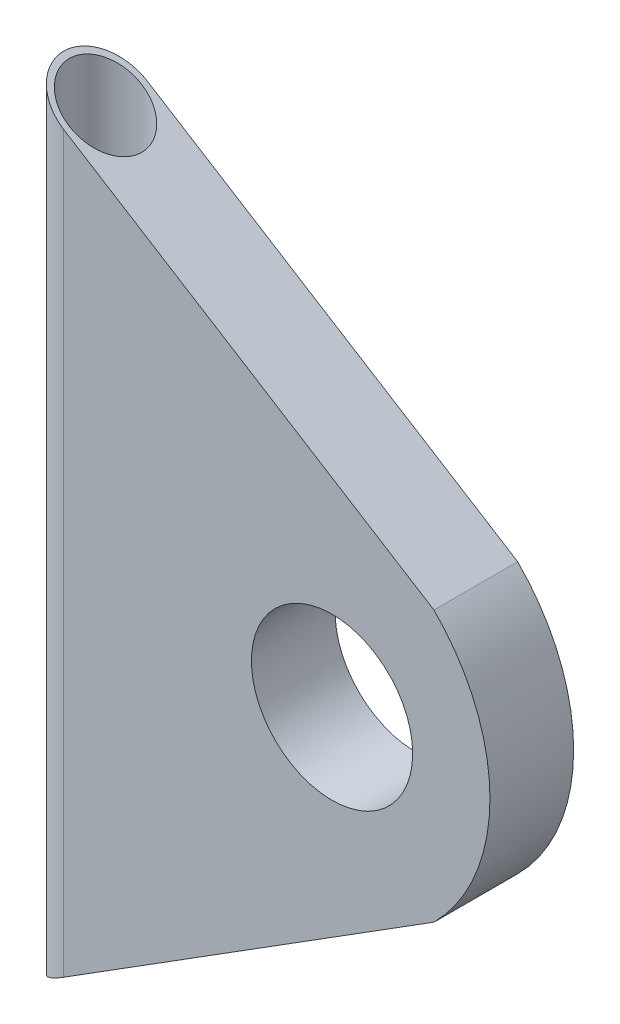
SolidWorks part; units mm, degrees
ref_plane "Piano frontale" through (0, 0, 0) normal (0, 0, 1) x (1, 0, 0)
ref_plane "Piano superiore" through (0, 0, 0) normal (0, 1, 0) x (1, 0, 0)
ref_plane "Piano destro" through (0, 0, 0) normal (1, 0, 0) x (0, 0, -1)
sketch "Schizzo1" plane through (0, 0, 0) normal (0, 0, 1) x (1, 0, 0)
  line L0 (0, 13.0495) -> (0, -13.2681)
  line L1 (0, -13.2681) -> (13.2739, -4.9218)
  line L2 (0, 13.0495) -> (13.2739, 4.7706)
  arc A0 (13.2739, -4.9218) -> (13.2739, 4.7706) centre (8.4277, -0.0756) ccw
  circle A1 centre (9.6206, -0.0756) radius 2.89
extrude "Estrusione-Estrusione1" add sketch "Schizzo1" along normal mid plane 3
sketch "Schizzo2" plane through (0, 0, 0) normal (0, 1, 0) x (1, 0, 0)
  circle A0 centre (0, 0) radius 1.5
extrude "Estrusione-Estrusione3" add sketch "Schizzo2" against normal up to surface and the other way up to surface up to face at (6.6369, -9.095, 0) other way up to face at (6.6369, 8.9101, 0)
sketch "Schizzo4" plane through (0, 0, 0) normal (0, 1, 0) x (1, 0, 0)
  circle A0 centre (0, 0) radius 1.2978
extrude "Taglio-Estrusione2" cut sketch "Schizzo4" against normal up to surface and the other way up to surface up to face at (6.2619, -9.3308, 0) other way up to face at (6.2619, 9.144, 0)
